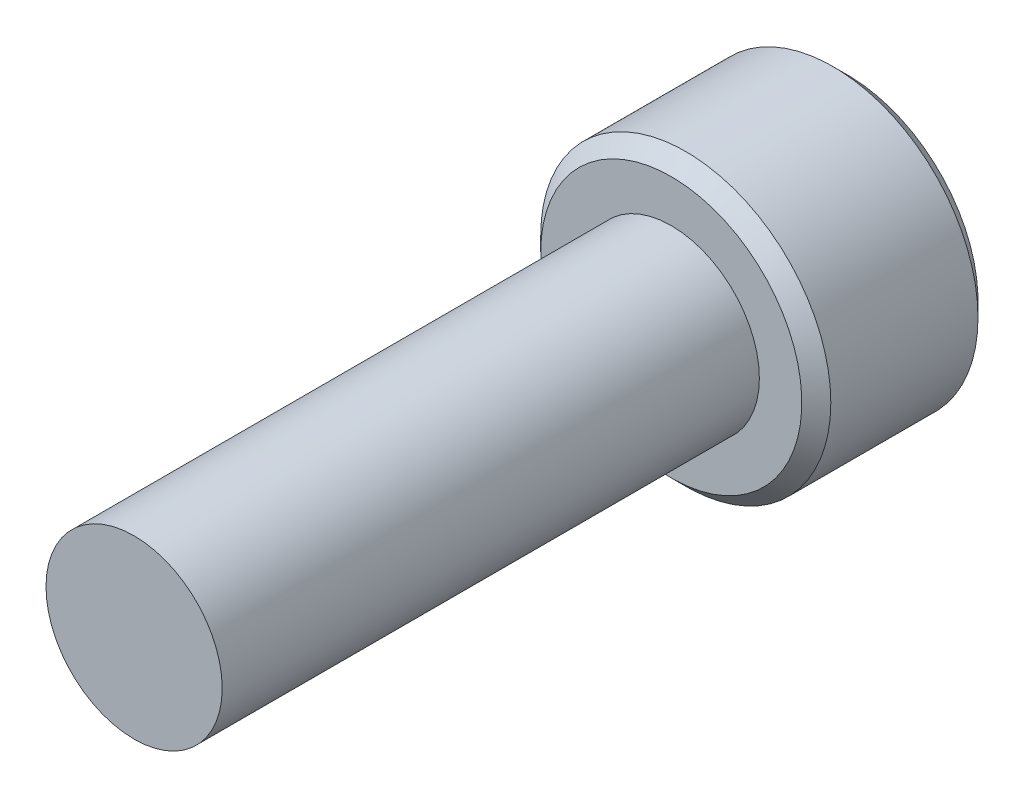
SolidWorks part; units mm, degrees
other "DetailItem1"
ref_plane "Front Plane" through (0, 0, 0) normal (0, 0, 1) x (1, 0, 0)
ref_plane "Top Plane" through (0, 0, 0) normal (0, 1, 0) x (1, 0, 0)
ref_plane "Right Plane" through (0, 0, 0) normal (1, 0, 0) x (0, 0, -1)
sketch "Sketch1" plane through (0, 0, 0) normal (0, 0, 1) x (1, 0, 0)
  circle A0 centre (0, 0) radius 2.0828
  dimension "OD" = 4.1656
extrude "Extrude1" add sketch "Sketch1" against normal blind 12.7
sketch "Sketch2" plane through (0, 0, 0) normal (0, 0, 1) x (1, 0, 0)
  circle A0 centre (0, 0) radius 2.0828 construction
  circle A1 centre (0, 0) radius 2.0828
curve "Helix/Spiral1" pitch 0.7937 height 13.4937 turns 17 parameters "pitch"=0.7937
sketch "Sketch3" [suppressed] plane through (0, 0, 0) normal (1, 0, 0) x (0, 0, -1)
  line L0 (-0.6945, 2.0828) -> (-0.3969, 1.5672)
  line L1 (-0.3969, 1.5672) -> (-0.2977, 1.5672)
  line L2 (-0.2977, 1.5672) -> (0, 2.0828)
  line L3 (-0.6945, 2.0828) -> (0, 2.0828)
  line L4 (-0.3473, 2.0828) -> (-0.3473, 1.5672) construction
  line L5 (-0.5457, 1.825) -> (-0.1488, 1.825) construction
  line L6 (0, 2.0828) -> (0, -2.0828) construction
  dimension "D1" = 0.0992
  dimension "D2" = 0.3969
  dimension "D3" = 60
sweep "Cut-Sweep1" [suppressed] cut profiles "Sketch3" path "Helix/Spiral1"
sketch "Sketch4" [suppressed] plane through (0, 0, 0) normal (1, 0, 0) x (0, 0, -1)
  line L0 (0.5388, 2.0828) -> (0, 1.3132)
  line L1 (0, 1.3132) -> (0, 2.0828)
  line L2 (0.5388, 2.0828) -> (0, 2.0828)
  line L3 (-0.6945, 2.0828) -> (0, 2.0828) construction
  line L4 (0, 0) -> (7.0209, 0) construction
  dimension "D1" = 55
  dimension "D2" = 0.254
revolve "Cut-Revolve1" [suppressed] cut sketch "Sketch4" angle 360 about L4
sketch "Sketch5" [suppressed] plane through (0, 0, 0) normal (1, 0, 0) x (0, 0, -1)
  line L0 (12.7, -1.5805) -> (12.7, 1.4861) construction
  line L1 (12.7, 2.2098) -> (0.1202, 2.2098)
  line L2 (12.7, 2.2098) -> (12.7, 0)
  line L3 (12.7, 0) -> (0, 0)
  line L4 (0, 1.8796) -> (0, 0)
  line L5 (0.1202, 2.2098) -> (0, 1.8796)
  line L6 (0, 0) -> (9.9695, 0) construction
  point P3 (0, 2.2098)
  point P10 (0, 2.2098)
  dimension "D1" = 0.3302
  dimension "D2" = 0.127
  dimension "D3" = 20
  dimension "Min Thread" = 0
revolve "partially thread" [suppressed] add sketch "Sketch5" angle 360 about L6
sketch "Sketch6" plane through (0, 0, -12.7) normal (0, 0, -1) x (-1, 0, 0)
  circle A0 centre (0, 0) radius 3.429
  dimension "head dia" = 6.858
extrude "Extrude2" add sketch "Sketch6" along normal blind 4.1656
sketch "Sketch7" plane through (0, 0, -16.8656) normal (0, 0, -1) x (-1, 0, 0)
  line L1 (0, 2.0622) -> (-1.7859, 1.0311)
  line L2 (-1.7859, 1.0311) -> (-1.7859, -1.0311)
  line L3 (-1.7859, -1.0311) -> (0, -2.0622)
  line L4 (0, -2.0622) -> (1.7859, -1.0311)
  line L5 (1.7859, -1.0311) -> (1.7859, 1.0311)
  line L6 (1.7859, 1.0311) -> (0, 2.0622)
  circle A0 centre (0, 0) radius 1.7859 construction
  dimension "hex dia" = 3.5719
extrude "Cut-Extrude1" cut sketch "Sketch7" against normal blind 2.6789
sketch "Sketch8" plane through (0, 0, -16.8656) normal (0, 0, -1) x (-1, 0, 0)
  circle A0 centre (0, 0) radius 2.0622
extrude "Cut-Extrude2" cut sketch "Sketch8" against normal through all draft 45
chamfer "Chamfer1" distance 0.3429 angle 45 2 edges at (-3.429, 0, -16.8656) (-3.429, 0, -12.7)
sketch "Sketch9" [suppressed] plane through (0, 0, 0) normal (1, 0, 0) x (0, 0, -1)
  line L0 (0, 2.0828) -> (0, -2.0828) construction
  line L1 (1.9844, 2.0828) -> (1.9844, -2.0828) construction
  dimension "D1" = 1.9844
equation "\"D3@Helix/Spiral1\" = \"screw length@Extrude1\"+\"pitch@Helix/Spiral1\""
equation "\"D1@Sketch3\" = \"pitch@Helix/Spiral1\"*.125"
equation "\"D2@Sketch3\" = \"pitch@Helix/Spiral1\"*.5"
equation "\"D1@Cut-Extrude1\" = \"hex dia@Sketch7\"*.75"
equation "\"D1@Chamfer1\" = \"head dia@Sketch6\"*.05"
equation "\"D1@Sketch9\" = \"pitch@Helix/Spiral1\"*2.5"
